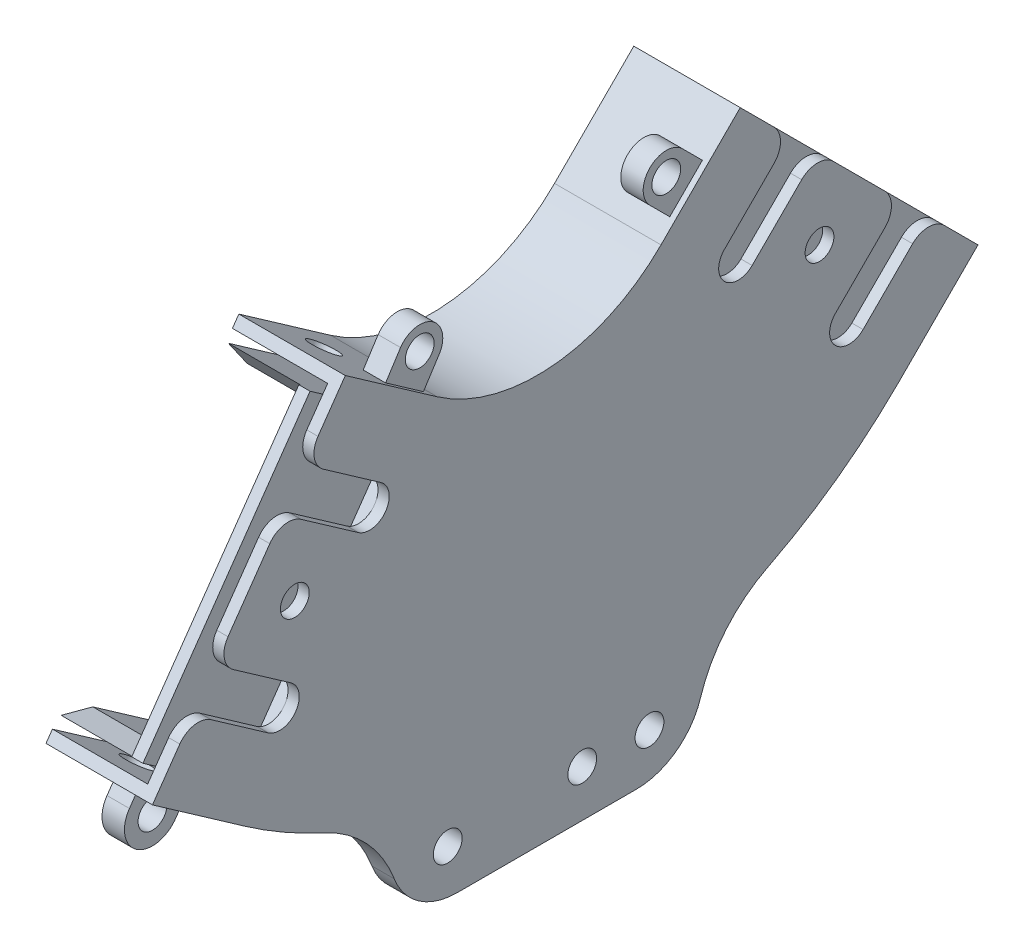
SolidWorks part; units mm, degrees
ref_plane "Front Plane" through (0, 0, 0) normal (0, 0, 1) x (1, 0, 0)
ref_plane "Top Plane" through (0, 0, 0) normal (0, 1, 0) x (1, 0, 0)
ref_plane "Right Plane" through (0, 0, 0) normal (1, 0, 0) x (0, 0, -1)
sketch "Sketch3" plane through (0, 0, 0) normal (1, 0, 0) x (0, 0, -1)
  line L0 (-22.7274, -32.4581) -> (-62.0633, -88.6355)
  line L1 (28.0184, -28.0184) -> (76.5118, -76.5118)
  line L2 (-22.7274, -32.4581) -> (0, 0) construction
  line L3 (0, 0) -> (28.0184, -28.0184) construction
  line L4 (0, 40.513) -> (0, -40.513) construction
  line L5 (-62.0633, -88.6355) -> (-66.4339, -94.8775)
  line L6 (76.5118, -76.5118) -> (81.8999, -81.8999)
  arc A2 (-62.0633, -88.6355) -> (76.5118, -76.5118) centre (0, 0) ccw
  arc A4 (-27.098, -38.7) -> (33.4066, -33.4066) centre (0, 0) ccw
  arc A5 (-22.7274, -32.4581) -> (28.0184, -28.0184) centre (0, 0) ccw
  arc A6 (-66.4339, -94.8775) -> (81.8999, -81.8999) centre (0, 0) ccw
  dimension "D1" = 216.408
  dimension "D2" = 135
  dimension "D3" = 94.488
  dimension "D4" = 7.62
  dimension "D6" = 7.62
  dimension "D5" = 80
extrude "Base extrude" add sketch "Sketch3" along normal blind 58.42 contours L5 A6 L6 A2 | A5 L0 A4 L1 region at (0, -39.9408, -3.4944) region at (0, -109.321, -9.5643)
sketch "Sketch4" plane through (58.42, 0, 0) normal (1, 0, 0) x (0, 0, -1)
  line L0 (-66.4339, -94.8775) -> (-22.7274, -32.4581)
  line L1 (28.0184, -28.0184) -> (81.8999, -81.8999)
  arc A0 (-22.7274, -32.4581) -> (28.0184, -28.0184) centre (0, 0) ccw
  arc A1 (-22.7274, -32.4581) -> (28.0184, -28.0184) centre (0, 0) ccw construction
  arc A2 (-66.4339, -94.8775) -> (81.8999, -81.8999) centre (0, 0) ccw
  arc A3 (-66.4339, -94.8775) -> (81.8999, -81.8999) centre (0, 0) ccw construction
  arc M1 (28.0184, -28.0184) -> (-22.7274, -32.4581) centre (0, 0) cw
  line M2 (-22.7274, -32.4581) -> (-27.098, -38.7)
  arc M3 (-27.098, -38.7) -> (33.4066, -33.4066) centre (0, 0) ccw
  line M4 (33.4066, -33.4066) -> (28.0184, -28.0184)
extrude "Outer wall" add sketch "Sketch4" along normal blind 7.62 contours L0 A2 L1 M3 | M4 M1 M2 M3 region at (58.42, -79.1939, -6.9286) region at (58.42, -39.9408, -3.4944)
ref_plane "Midplane" through (29.21, 0, 0) normal (-1, 0, 0) x (0, 0, 1)
mirror "Mirror1" about plane through (29.21, 0, 0) normal (-1, 0, 0) of "Outer wall"
sketch "Sketch6" plane through (0, 0, 0) normal (0, 0.5736, 0.8192) x (1, 0, 0)
  line L27 (-5.08, -42.164) -> (63.5, -42.164)
  line L28 (-5.08, -42.164) -> (-5.08, -113.284)
  line L29 (-5.08, -113.284) -> (63.5, -113.284)
  line L30 (63.5, -42.164) -> (63.5, -113.284)
  line L31 (-2.54, -44.704) -> (60.96, -44.704)
  line L32 (-2.54, -44.704) -> (-2.54, -110.744)
  line L33 (-2.54, -110.744) -> (60.96, -110.744)
  line L34 (60.96, -44.704) -> (60.96, -110.744)
  line L35 (58.42, -47.244) -> (0, -47.244) construction
  line L36 (0, -108.204) -> (0, -18.7894) construction
  line L37 (58.42, -18.7894) -> (58.42, -108.204) construction
  line L38 (58.42, -108.204) -> (0, -108.204) construction
  line L40 (0, -47.244) -> (58.42, -47.244)
  line L41 (0, -47.244) -> (0, -108.204)
  line L42 (0, -108.204) -> (58.42, -108.204)
  line L43 (58.42, -47.244) -> (58.42, -108.204)
  line L44 (-7.62, -39.624) -> (66.04, -39.624)
  line L45 (-7.62, -39.624) -> (-7.62, -115.824)
  line L46 (-7.62, -115.824) -> (66.04, -115.824)
  line L47 (66.04, -39.624) -> (66.04, -115.824)
  line M21 (-7.62, -39.624) -> (-7.62, -115.824)
  line M22 (-7.62, -115.824) -> (66.04, -115.824)
  line M23 (66.04, -115.824) -> (66.04, -39.624)
  line M24 (66.04, -39.624) -> (-7.62, -39.624)
  line M25 (58.42, -108.204) -> (0, -108.204)
  line M26 (0, -108.204) -> (0, -47.244)
  line M27 (0, -47.244) -> (58.42, -47.244)
  line M28 (58.42, -47.244) -> (58.42, -108.204)
  dimension "D1" = 2.54
  dimension "D2" = 2.54
  dimension "D3" = 2.54
  dimension "D4" = 2.54
  dimension "D5" = 2.54
  dimension "D6" = 2.54
  dimension "D7" = 2.54
  dimension "D8" = 2.54
extrude "Endcap 1" add sketch "Sketch6" along normal blind 25.4 contours L27 L30 L29 L28 M24 M21 M22 M23 | L34 L31 L32 L33 M28 M25 M26 M27 region at (29.21, -37.3698, 26.1667) region at (29.21, -33.3262, 23.3353)
sketch "Sketch7" plane through (0, 0, 0) normal (0, 0.7071, -0.7071) x (1, 0, 0)
  line L0 (-5.08, 113.284) -> (63.5, 113.284)
  line L1 (-5.08, 113.284) -> (-5.08, 42.164)
  line L2 (-5.08, 42.164) -> (63.5, 42.164)
  line L3 (63.5, 113.284) -> (63.5, 42.164)
  line L4 (-2.54, 110.744) -> (60.96, 110.744)
  line L5 (-2.54, 110.744) -> (-2.54, 44.704)
  line L6 (-2.54, 44.704) -> (60.96, 44.704)
  line L7 (60.96, 110.744) -> (60.96, 44.704)
  line L8 (0, 108.204) -> (58.42, 108.204)
  line L9 (0, 108.204) -> (0, 47.244)
  line L10 (0, 47.244) -> (58.42, 47.244)
  line L11 (58.42, 108.204) -> (58.42, 47.244)
  line L12 (-7.62, 115.824) -> (66.04, 115.824)
  line L13 (-7.62, 115.824) -> (-7.62, 39.624)
  line L14 (-7.62, 39.624) -> (66.04, 39.624)
  line L15 (66.04, 115.824) -> (66.04, 39.624)
  line L16 (58.42, 108.204) -> (0, 108.204) construction
  line L17 (58.42, 47.244) -> (58.42, 108.204) construction
  line L18 (66.04, 115.824) -> (-7.62, 115.824) construction
  line L19 (66.04, 39.624) -> (66.04, 115.824) construction
  line L20 (-7.62, 39.624) -> (-7.62, 115.824) construction
  line L21 (66.04, 39.624) -> (-7.62, 39.624) construction
  line M17 (66.04, 115.824) -> (-7.62, 115.824)
  line M18 (-7.62, 115.824) -> (-7.62, 39.624)
  line M19 (-7.62, 39.624) -> (66.04, 39.624)
  line M20 (66.04, 39.624) -> (66.04, 115.824)
  line M21 (0, 47.244) -> (0, 108.204)
  line M22 (0, 108.204) -> (58.42, 108.204)
  line M23 (58.42, 108.204) -> (58.42, 47.244)
  line M24 (58.42, 47.244) -> (0, 47.244)
  dimension "D1" = 2.54
  dimension "D2" = 2.54
  dimension "D3" = 2.54
  dimension "D4" = 2.54
  dimension "D5" = 2.54
  dimension "D6" = 2.54
  dimension "D7" = 2.54
  dimension "D8" = 2.54
extrude "Endcap 2" add sketch "Sketch7" along normal blind 25.4 contours L0 L3 L2 L1 M20 M17 M18 M19 | L7 L4 L5 L6 M24 M21 M22 M23 region at (29.21, -77.66, -77.66) region at (29.21, -81.1505, -81.1505)
chamfer "Internal Chamfer" distance 7.62 angle 20 4 edges at (29.21, -74.0667, 82.8697) (29.21, -24.1312, 47.9045) (29.21, -58.5513, -94.4723) (29.21, -15.446, -51.3671) first distance on face at (29.21, -81.3511, 72.4665) first distance on face at (29.21, -31.4156, 37.5013) first distance on face at (29.21, -67.5315, -85.492) first distance on face at (29.21, -24.4263, -42.3868)
ref_plane "Plane2" through (0, -13.9736, -1.2225) normal (0, -0.9962, -0.0872) x (-1, 0, 0)
sketch "Sketch10" plane through (0, -13.9736, -1.2225) normal (0, -0.9962, -0.0872) x (-1, 0, 0)
  line L0 (-66.04, 93.9078) -> (7.62, 93.9078) construction
  line L1 (-16.51, 95.5358) -> (-41.91, 95.5358)
  line L2 (-16.51, 95.5358) -> (-16.51, -82.1857)
  line L3 (-16.51, -82.1857) -> (-41.91, -82.1857)
  line L4 (-41.91, 95.5358) -> (-41.91, -82.1857)
  point P4 (-29.21, 93.9078)
  point P5 (-29.21, 95.5358)
  dimension "D1" = 25.4
extrude "Flywheel Hole" cut sketch "Sketch10" along normal up to next
sketch "Sketch11" plane through (-7.62, 0, 0) normal (-1, 0, 0) x (0, 0, 1)
  line L0 (-25.2982, 2.2719) -> (-28.0184, -28.0184)
  line L4 (-3.0636, -22.3183) -> (-4.5937, -39.3568)
  line L5 (6.8995, -21.445) -> (11.3704, -37.9575)
  line L6 (-20.4217, -1.79) -> (20.4217, 1.79) construction
  line L7 (24.5172, 6.6383) -> (33.1306, -25.1737)
  line L8 (43.5339, -17.8892) -> (22.7274, -32.4581) construction
  line L10 (1.5525, -17.7121) -> (-2.2178, 25.303) construction
  line L11 (22.7274, -32.4581) -> (43.5339, -17.8892)
  line L12 (22.7274, -32.4581) -> (33.1306, -25.1737)
  arc A1 (-28.0184, -28.0184) -> (22.7274, -32.4581) centre (0, 0) ccw construction
  circle A3 centre (0, 0) radius 4.064
  arc A4 (24.5172, 6.6383) -> (-25.2982, 2.2719) centre (0, 0) ccw
  circle A6 centre (-20.4217, -1.79) radius 2.5
  circle A7 centre (20.4217, 1.79) radius 2.5
  arc A8 (-3.0636, -22.3183) -> (6.8995, -21.445) centre (1.9961, -22.7727) cw
  arc A11 (11.3704, -37.9575) -> (22.7274, -32.4581) centre (0, 0) ccw
  arc A12 (-28.0184, -28.0184) -> (22.7274, -32.4581) centre (0, 0) ccw
  arc A13 (-28.0184, -28.0184) -> (-4.5937, -39.3568) centre (0, 0) ccw
  point P22 (0, 0)
  dimension "D3" = 8.128
  dimension "D2" = 25.4
  dimension "D1" = 5
  dimension "D5" = 5.08
  dimension "D4" = 41
  dimension "D7" = 43.18
  dimension "D6" = 0
extrude "Flywheel holder" add sketch "Sketch11" against normal blind 7.62
sketch "Sketch12" plane through (-7.62, 0, 0) normal (-1, 0, 0) x (0, 0, 1)
  circle A0 centre (0, 0) radius 14.605
  dimension "D1" = 29.21
extrude "Motor insert" cut sketch "Sketch12" against normal blind 6.35
sketch "Sketch14" plane through (-7.62, 0, 0) normal (-1, 0, 0) x (0, 0, 1)
  line L1 (-106.5763, 40.9543) -> (105.556, 40.9543)
  line L2 (-106.5763, 40.9543) -> (-106.5763, -120.0185)
  line L3 (-106.5763, -120.0185) -> (105.556, -120.0185)
  line L4 (105.556, 40.9543) -> (105.556, -120.0185)
extrude "Cut-Extrude2" cut sketch "Sketch14" against normal up to surface (49.53 mm away) up to face at (41.91, -26.9401, -2.3569)
sketch "Sketch15" plane through (41.91, 0, 0) normal (-1, 0, 0) x (0, 0, 1)
  line L0 (-93.8083, -77.7308) -> (-89.6212, -74.1787)
  line L1 (-99.8604, -63.9394) -> (-81.8999, -81.8999) construction
  line L2 (-89.6212, -74.1787) -> (-80.6312, -83.1493)
  line L3 (-80.6312, -83.1493) -> (-85.0539, -86.9012)
  line L4 (-16.51, -121.4959) -> (-16.51, -114.6413)
  line L5 (-16.51, -114.6413) -> (-3.8593, -115.7597)
  line L6 (-3.8593, -115.7597) -> (-3.8593, -120.7059)
  line L7 (63.1155, -104.8839) -> (59.3284, -99.4753)
  line L8 (59.3284, -99.4753) -> (69.9059, -92.4464)
  line L9 (66.4339, -94.8775) -> (87.2404, -80.3086) construction
  line L10 (69.9059, -92.4464) -> (73.4123, -97.454)
  circle A0 centre (-89.7004, -82.5731) radius 3.2639
  circle A1 centre (-10.16, -121.4959) radius 3.2639
  circle A2 centre (68.1904, -101.0671) radius 3.2639
  arc A3 (-93.8083, -77.7308) -> (-85.0539, -86.9012) centre (-89.7004, -82.5731) ccw
  arc A5 (62.868, -104.5305) -> (73.3715, -97.3959) centre (68.1904, -101.0671) ccw
  arc A6 (-81.8999, -81.8999) -> (66.4339, -94.8775) centre (0, 0) ccw construction
  arc A7 (-16.51, -121.4959) -> (-3.8593, -120.7059) centre (-10.16, -121.4959) ccw
  line M28 (-99.8604, -63.9394) -> (-81.8999, -81.8999)
  arc M29 (-81.8999, -81.8999) -> (66.4339, -94.8775) centre (0, 0) ccw
  line M30 (66.4339, -94.8775) -> (87.2404, -80.3086)
  dimension "D4" = 6.5278
  dimension "D5" = 12.7
  dimension "D1" = 121.92
  dimension "D2" = 121.92
  dimension "D3" = 121.92
  dimension "D6" = 10.16
  dimension "D7" = 10.16
  dimension "D8" = 19.05
  dimension "D9" = 12.7
  dimension "D10" = 12.7
  dimension "D11" = 12.7
extrude "Joining screw holes" add sketch "Sketch15" against normal blind 5.08 contours L0 A3 L3 A0 M29 M28 | L4 A7 L6 A1 M29 | L7 A5 L10 A2 M30 M29 region at (41.91, -97.4205, 63.0391) region at (41.91, -115.5565, -10.2161) region at (41.91, -76.1174, -91.5767)
ref_plane "Plane3" through (59.69, 0, 0) normal (1, 0, 0) x (0, 0, -1)
sketch "Sketch16" plane through (59.69, 0, 0) normal (1, 0, 0) x (0, 0, -1)
  line L0 (-43.5339, -17.8892) -> (-22.7274, -32.4581) construction
  line L1 (45.9789, -10.0579) -> (28.0184, -28.0184) construction
  line L2 (-29.7459, -19.9251) -> (-33.1306, -25.1737)
  line L3 (-33.1306, -25.1737) -> (-24.5641, -31.172)
  line L4 (-24.5641, -31.172) -> (-21.1794, -25.9235)
  line L5 (26.7818, -20.2747) -> (31.2719, -24.7649)
  line L6 (31.2719, -24.7649) -> (38.6683, -17.3685)
  line L7 (38.6683, -17.3685) -> (34.1782, -12.8783)
  line L8 (34.1782, -12.8783) -> (26.7818, -20.2747) construction
  circle A0 centre (-25.4, -22.8348) radius 3.2639
  circle A1 centre (30.48, -16.5765) radius 3.2639
  arc A2 (-21.1794, -25.9235) -> (-29.8435, -20.0764) centre (-25.4, -22.8348) ccw
  arc A3 (34.1782, -12.8783) -> (26.7818, -20.2747) centre (30.48, -16.5765) ccw
  dimension "D3" = 6.5278
  dimension "D1" = 6.35
  dimension "D2" = 6.35
  dimension "D4" = 25.4
  dimension "D5" = 30.48
  dimension "D6" = 55.88
  dimension "D7" = 6.2582
extrude "Flywheel cover connectors" add sketch "Sketch16" along normal blind 5.08 contours L4 A2 L2 L3 A0 | L7 L8 A1 L5 L6 | L8 A3 A1 region at (59.69, -18.7043, 22.5078) region at (59.69, -19.2478, -33.1513) region at (59.69, -12.9676, -26.8711)
sketch "Sketch17" plane through (66.04, 0, 0) normal (1, 0, 0) x (0, 0, -1)
  line L0 (-30.48, -111.7415) -> (-30.48, -132.08)
  line L1 (-30.48, -132.08) -> (35.56, -132.08)
  line L2 (35.56, -132.08) -> (35.56, -110.2301)
  circle A0 centre (-20.32, -121.92) radius 3.2639
  circle A1 centre (25.4, -121.92) radius 3.2639
  arc A2 (-66.4339, -94.8775) -> (81.8999, -81.8999) centre (0, 0) ccw construction
  circle A4 centre (10.16, -121.4959) radius 3.2639
  arc A5 (-66.4339, -94.8775) -> (81.8999, -81.8999) centre (0, 0) ccw
  arc A6 (-30.48, -111.7415) -> (35.56, -110.2301) centre (0, 0) ccw
  circle A7 centre (10.16, -121.4959) radius 3.2639 construction
  dimension "D1" = 6.5278
  dimension "D2" = 20.32
  dimension "D3" = 25.4
  dimension "D4" = 121.92
  dimension "D5" = 0
  dimension "D6" = 10.16
  dimension "D7" = 10.16
  dimension "D8" = 10.16
extrude "80-20 connector" add sketch "Sketch17" against normal blind 5.08
fillet "Fillet1" radius 30.48 2 edges at (63.5, -111.7415, 30.48) (63.5, -110.2301, -35.56)
fillet "Fillet2" radius 15.24 2 edges at (63.5, -132.08, -35.56) (63.5, -132.08, 30.48)
sketch "Sketch18" plane through (66.04, 0, 0) normal (1, 0, 0) x (0, 0, -1)
  line L0 (-35.474, -42.9126) -> (-52.6394, -30.8933)
  line L1 (-87.2404, -80.3086) -> (-43.5339, -17.8892) construction
  line L2 (-52.6394, -30.8933) -> (-57.7385, -38.1755)
  line L3 (-57.7385, -38.1755) -> (-40.5731, -50.1948)
  line L4 (-55.8704, -72.0416) -> (-73.0358, -60.0223)
  line L5 (-73.0358, -60.0223) -> (-78.1349, -67.3046)
  line L6 (-78.1349, -67.3046) -> (-60.9695, -79.3239)
  line L7 (42.3868, -36.1006) -> (57.2042, -21.2832)
  line L8 (45.9789, -10.0579) -> (99.8604, -63.9394) construction
  line L9 (57.2042, -21.2832) -> (63.4904, -27.5694)
  line L10 (63.4904, -27.5694) -> (48.673, -42.3868)
  line L11 (67.5315, -61.2453) -> (82.3489, -46.4279)
  line L12 (82.3489, -46.4279) -> (88.6351, -52.7141)
  line L13 (88.6351, -52.7141) -> (73.8177, -67.5315)
  line L14 (-43.5339, -17.8892) -> (-22.7274, -32.4581) construction
  line L15 (45.9789, -10.0579) -> (28.0184, -28.0184) construction
  line L16 (99.8604, -63.9394) -> (81.8999, -81.8999) construction
  line L17 (-87.2404, -80.3086) -> (-66.4339, -94.8775) construction
  line L18 (-24.1843, -34.5387) -> (-64.977, -92.7968) construction
  arc A0 (-40.5731, -50.1948) -> (-35.474, -42.9126) centre (-38.0236, -46.5537) ccw
  arc A1 (-60.9695, -79.3239) -> (-55.8704, -72.0416) centre (-58.42, -75.6827) ccw
  arc A2 (42.3868, -36.1006) -> (48.673, -42.3868) centre (45.5299, -39.2437) ccw
  arc A3 (67.5315, -61.2453) -> (73.8177, -67.5315) centre (70.6746, -64.3884) ccw
  dimension "D1" = 8.89
  dimension "D3" = 20.32
  dimension "D4" = 20.32
  dimension "D5" = 20.32
  dimension "D6" = 20.32
extrude "Support Removal" cut sketch "Sketch18" against normal up to next
fillet "Fillet3" radius 5.08 8 edges at (64.77, -52.7141, -88.6351) (64.77, -46.4279, -82.3489) (64.77, -27.5694, -63.4904) (64.77, -21.2832, -57.2042) (64.77, -67.3046, 78.1349) (64.77, -60.0223, 73.0358) (64.77, -38.1755, 57.7385) (64.77, -30.8933, 52.6394)
sketch "Sketch19" plane through (66.04, 0, 0) normal (1, 0, 0) x (0, 0, -1)
  line L0 (-70.122, -55.861) -> (-60.6522, -42.3368) construction
  line L1 (67.0825, -31.1615) -> (78.7568, -42.8358) construction
  line L2 (-65.3871, -49.0989) -> (-54.9839, -56.3834) construction
  line L3 (-34.3825, -49.1033) -> (-54.7788, -78.2323) construction
  line L4 (67.5315, -67.5315) -> (42.3868, -42.3868) construction
  line L5 (72.9197, -36.9987) -> (63.9394, -45.9789) construction
  circle A0 centre (-54.9839, -56.3834) radius 3.2639
  circle A1 centre (63.9394, -45.9789) radius 3.2639
  point P4 (-65.3871, -49.0989)
  point P5 (72.9197, -36.9987)
  dimension "D1" = 6.5278
  dimension "D2" = 12.7
  dimension "D3" = 12.7
extrude "Cut-Extrude3" cut sketch "Sketch19" against normal up to next contours A1 | A0 region at (66.04, -56.3834, 54.9839) region at (66.04, -45.9789, -63.9394)
sketch "Sketch20" plane through (0, -94.8775, 66.4339) normal (0, -0.8192, 0.5736) x (1, 0, 0)
  line L0 (63.5, 25.4) -> (63.5, 0) construction
  line L1 (41.91, 0) -> (63.5, 0) construction
  circle A0 centre (50.8, 12.7) radius 3.2639
  dimension "D1" = 6.5278
  dimension "D2" = 12.7
  dimension "D3" = 12.7
extrude "Cut-Extrude4" cut sketch "Sketch20" against normal up to next
ref_plane "Plane4" through (0, -63.6678, 44.5807) normal (0, 0.8192, -0.5736) x (1, 0, 0)
mirror "Mirror2" about plane through (0, -63.6678, 44.5807) normal (0, 0.8192, -0.5736) of "Cut-Extrude4"
sketch "Sketch21" plane through (0, -81.8999, -81.8999) normal (0, -0.7071, -0.7071) x (1, 0, 0)
  line L0 (66.04, 0) -> (46.99, 0) construction
  line L1 (63.5, -25.4) -> (63.5, 0) construction
  circle A0 centre (50.8, -12.7) radius 3.2639
  dimension "D1" = 6.5278
  dimension "D2" = 12.7
  dimension "D3" = 12.7
extrude "Cut-Extrude5" cut sketch "Sketch21" against normal up to next contours A0
